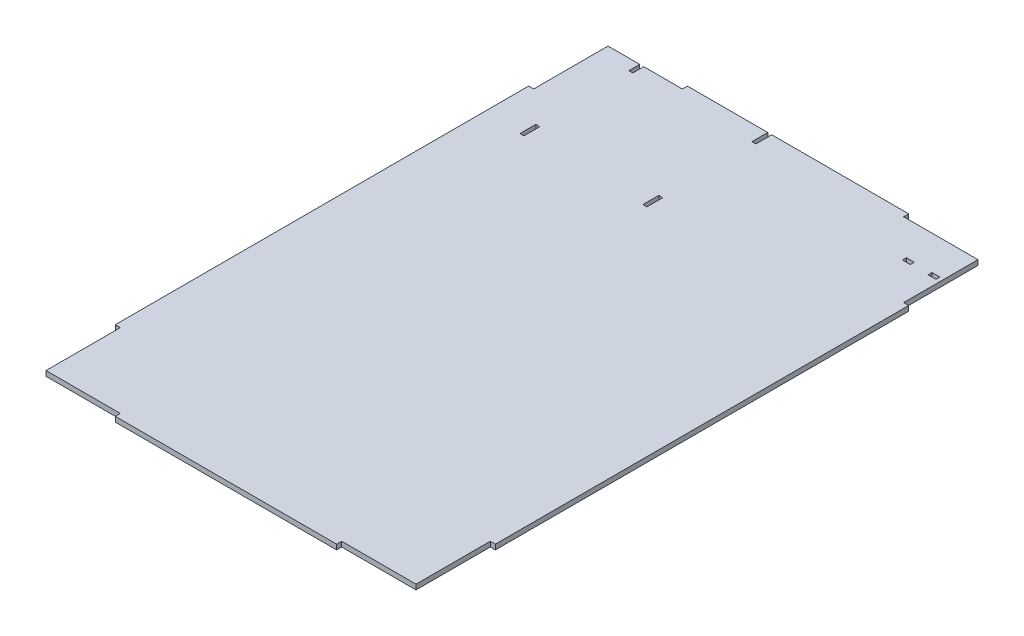
SolidWorks part; units mm, degrees
ref_plane "Front Plane" through (0, 0, 0) normal (0, 0, 1) x (1, 0, 0)
ref_plane "Top Plane" through (0, 0, 0) normal (0, 1, 0) x (1, 0, 0)
ref_plane "Right Plane" through (0, 0, 0) normal (1, 0, 0) x (0, 0, -1)
sketch "Sketch1" plane through (0, 0, 0) normal (0, 1, 0) x (1, 0, 0)
  line L7 (-239.5, -360.5) -> (239.5, -360.5)
  line L8 (-239.5, -360.5) -> (-239.5, 360.5)
  line L9 (-239.5, 360.5) -> (239.5, 360.5)
  line L10 (239.5, -360.5) -> (239.5, 360.5)
  point P0 (0, 0)
  point P3 (239.5, 0)
  point P6 (0, 0)
  point P11 (0, -360.5)
  dimension "D1" = 721
  dimension "D2" = 479
extrude "Boss-Extrude1" add sketch "Sketch1" along normal mid plane 6.35
sketch "Sketch2" plane through (0, 3.175, 0) normal (0, 1, 0) x (1, 0, 0)
  line L0 (-239.5, 360.5) -> (-239.5, 260.5)
  line L1 (-239.5, 360.5) -> (-239.5, -360.5) construction
  line L2 (-239.5, 260.5) -> (-233.15, 260.5)
  line L3 (-233.15, 260.5) -> (-233.15, 354.15)
  line L4 (-233.15, 354.15) -> (-139.5, 354.15)
  line L5 (-139.5, 354.15) -> (-139.5, 360.5)
  line L6 (239.5, 360.5) -> (-239.5, 360.5) construction
  line L7 (-139.5, 360.5) -> (-239.5, 360.5)
  line L8 (239.5, 360.5) -> (139.5, 360.5)
  line L9 (139.5, 360.5) -> (139.5, 354.15)
  line L10 (139.5, 354.15) -> (233.15, 354.15)
  line L11 (233.15, 354.15) -> (233.15, 260.5)
  line L12 (233.15, 260.5) -> (239.5, 260.5)
  line L13 (239.5, -360.5) -> (239.5, 360.5) construction
  line L14 (239.5, 260.5) -> (239.5, 360.5)
  line L15 (239.5, -360.5) -> (239.5, -260.5)
  line L16 (239.5, -260.5) -> (233.15, -260.5)
  line L17 (233.15, -260.5) -> (233.15, -354.15)
  line L18 (233.15, -354.15) -> (139.5, -354.15)
  line L19 (139.5, -354.15) -> (139.5, -360.5)
  line L20 (-239.5, -360.5) -> (239.5, -360.5) construction
  line L21 (139.5, -360.5) -> (239.5, -360.5)
  line L22 (-239.5, -360.5) -> (-139.5, -360.5)
  line L23 (-139.5, -360.5) -> (-139.5, -354.15)
  line L24 (-139.5, -354.15) -> (-233.15, -354.15)
  line L25 (-233.15, -354.15) -> (-233.15, -260.5)
  line L26 (-233.15, -260.5) -> (-239.5, -260.5)
  line L27 (-239.5, -260.5) -> (-239.5, -360.5)
  dimension "D1" = 100
  dimension "D2" = 6.35
extrude "Cut-Extrude1" cut sketch "Sketch2" against normal through all
sketch "Sketch3" plane through (0, -3.175, 0) normal (0, -1, 0) x (1, 0, 0)
  line L0 (233.15, -354.15) -> (233.15, -260.5) construction
  line L1 (139.5, -354.15) -> (233.15, -354.15) construction
  line L2 (139.5, -360.5) -> (-139.5, -360.5) construction
  line L3 (-33.15, -360.5) -> (-38.15, -360.5)
  line L4 (-33.15, -360.5) -> (-33.15, -340.5)
  line L5 (-33.15, -340.5) -> (-38.15, -340.5)
  line L6 (-38.15, -360.5) -> (-38.15, -340.5)
  line L7 (-233.15, -260.5) -> (-233.15, -354.15) construction
  line L8 (185.85, -306.15) -> (195.85, -306.15)
  line L9 (185.85, -306.15) -> (185.85, -311.15)
  line L10 (185.85, -311.15) -> (195.85, -311.15)
  line L11 (195.85, -306.15) -> (195.85, -311.15)
  line L12 (228.15, -306.15) -> (228.15, -311.15)
  line L13 (218.15, -306.15) -> (228.15, -306.15)
  line L14 (218.15, -306.15) -> (218.15, -311.15)
  line L15 (218.15, -311.15) -> (228.15, -311.15)
  line L16 (-188.15, -360.5) -> (-193.15, -360.5)
  line L17 (-188.15, -360.5) -> (-188.15, -340.5)
  line L18 (-188.15, -340.5) -> (-193.15, -340.5)
  line L19 (-193.15, -360.5) -> (-193.15, -340.5)
  line L20 (-33.15, -223.15) -> (-38.15, -223.15)
  line L21 (-33.15, -223.15) -> (-33.15, -203.15)
  line L22 (-33.15, -203.15) -> (-38.15, -203.15)
  line L23 (-38.15, -223.15) -> (-38.15, -203.15)
  line L24 (-188.15, -223.15) -> (-193.15, -223.15)
  line L25 (-188.15, -223.15) -> (-188.15, -203.15)
  line L26 (-188.15, -203.15) -> (-193.15, -203.15)
  line L27 (-193.15, -223.15) -> (-193.15, -203.15)
  point P30 (-162.1564, -340.5)
  dimension "D1" = 10
  dimension "D2" = 5
  dimension "D3" = 5
  dimension "D4" = 42.3
  dimension "D5" = 43
  dimension "D6" = 5
  dimension "D7" = 20
  dimension "D8" = 117.35
  dimension "D9" = 150
  dimension "D10" = 45
extrude "Cut-Extrude2" cut sketch "Sketch3" against normal through all
